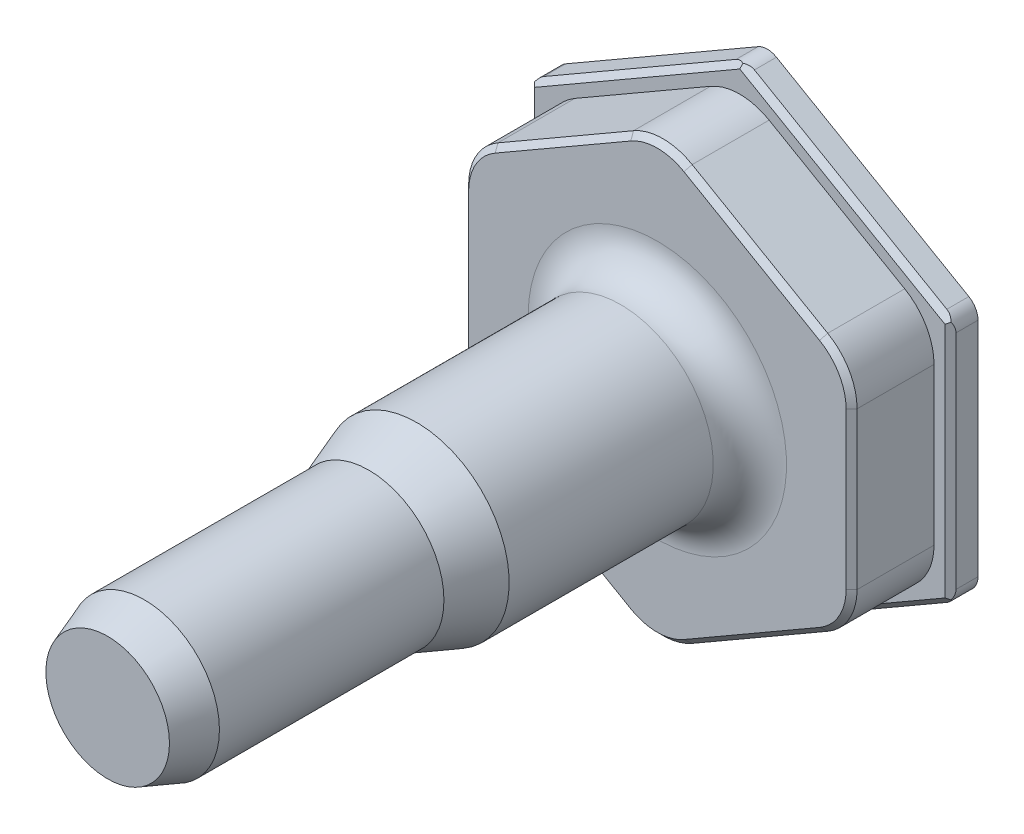
SolidWorks part; units mm, degrees
ref_plane "Front Plane" through (0, 0, 0) normal (0, 0, 1) x (1, 0, 0)
ref_plane "Top Plane" through (0, 0, 0) normal (0, 1, 0) x (1, 0, 0)
ref_plane "Right Plane" through (0, 0, 0) normal (1, 0, 0) x (0, 0, -1)
sketch "Sketch1" plane through (0, 0, 0) normal (0, 0, 1) x (1, 0, 0)
  line L12 (0, 12.2398) -> (10.6, 6.1199)
  line L14 (10.6, 6.1199) -> (10.6, -6.1199)
  line L15 (10.6, -6.1199) -> (0, -12.2398)
  line L16 (0, -12.2398) -> (-10.6, -6.1199)
  line L17 (-10.6, -6.1199) -> (-10.6, 6.1199)
  line L18 (-10.6, 6.1199) -> (0, 12.2398)
  line L19 (-11.5, 6.6395) -> (0, 13.2791)
  line L20 (0, 13.2791) -> (11.5, 6.6395)
  line L21 (11.5, 6.6395) -> (11.5, -6.6395)
  line L22 (11.5, -6.6395) -> (0, -13.2791)
  line L23 (0, -13.2791) -> (-11.5, -6.6395)
  line L24 (-11.5, -6.6395) -> (-11.5, 6.6395)
  circle A1 centre (0, 0) radius 3.25
  circle A2 centre (0, 0) radius 5.05
  circle A3 centre (0, 0) radius 2.125
  circle A4 centre (0, 0) radius 4.1
  point P3 (0, 12.2398)
  point P4 (10.6, 6.1199)
  point P7 (10.6, -6.1199)
  point P9 (0, -12.2398)
  point P10 (-10.6, -6.1199)
  point P12 (-10.6, 6.1199)
  point P13 (0, 0)
  dimension "D1" = 21.2
  dimension "D6" = 6.5
  dimension "D7" = 10.1
  dimension "D8" = 4.25
  dimension "D9" = 8.2
  dimension "D2" = 6
  dimension "D3" = 120
  dimension "D4" = 120
  dimension "D5" = 0.9
extrude "Boss-Extrude1" add sketch "Sketch1" along normal blind 1.5 contours L19 L20 L21 L22 L23 L24
ref_plane "Plane1" through (-11.5, -6.6395, 0) normal (-0.866, 0.5, 0) x (0, 0, 1)
ref_plane "Plane2" through (0, -13.2791, 0) normal (-0.866, 0.5, 0) x (0, 0, 1)
extrude "Boss-Extrude3" add sketch "Sketch1<8>" along normal blind 36 contours A4
sketch "Sketch1<8>" plane through (0, 0, 0) normal (0, 0, 1) x (1, 0, 0) same geometry as "Sketch1"
extrude "Boss-Extrude4" add sketch "Sketch1<9>" along normal blind 19 contours A2
sketch "Sketch1<9>" plane through (0, 0, 0) normal (0, 0, 1) x (1, 0, 0) same geometry as "Sketch1"
shell "Shell1" thickness 2
extrude "Cut-Extrude1" cut sketch "Sketch1<10>" along normal blind 17 contours A1
sketch "Sketch1<10>" plane through (0, 0, 0) normal (0, 0, 1) x (1, 0, 0) same geometry as "Sketch1"
extrude "Boss-Extrude2" add sketch "Sketch1<3>" along normal blind 6 contours L17 L18 L12 L14 L15 L16 | A1
sketch "Sketch1<3>" plane through (0, 0, 0) normal (0, 0, 1) x (1, 0, 0) same geometry as "Sketch1"
chamfer "Chamfer1" distance 2 angle 20 1 edges at (4.1, 0, 36) first distance on face at (4.1, 0, 19)
chamfer "Chamfer2" distance 1 angle 70 1 edges at (4.1, 0, 19) first distance on face at (4.1, 0, 19)
chamfer "Chamfer3" distance 0.7 angle 60 1 edges at (2.1, 0, 17) first distance on face at (2.1, 0, 17)
chamfer "Chamfer6" distance 0.3 angle 45 1 edges at (3.25, 0, 0)
ref_plane "Plane3" through (0, 0, 5) normal (0, 0, 1) x (1, 0, 0)
sketch "Sketch2" plane through (0, 0, 5) normal (0, 0, 1) x (1, 0, 0)
  line L1 (-17.7118, 13.112) -> (21.871, 13.112)
  line L2 (-17.7118, 13.112) -> (-17.7118, -17.4474)
  line L3 (-17.7118, -17.4474) -> (21.871, -17.4474)
  line L4 (21.871, 13.112) -> (21.871, -17.4474)
fillet "Fillet1" radius 3.2 6 edges at (10.6, -6.1199, 3.75) (0, -12.2398, 3.75) (-10.6, -6.1199, 3.75) (-10.6, 6.1199, 3.75) (0, 12.2398, 3.75) (10.6, 6.1199, 3.75)
chamfer "Chamfer5" distance 0.3 angle 45 18 edges at (-10.6, 0, 6) (-5.3, 9.1799, 6) (5.3, 9.1799, 6) (10.6, 0, 6) (5.3, -9.1799, 6) (-5.3, -9.1799, 6) (11.5, 0, 1.5) (5.75, -9.9593, 1.5) (-5.75, -9.9593, 1.5) (-11.5, 0, 1.5) (5.75, 9.9593, 1.5) (-5.75, 9.9593, 1.5) (0, -11.7448, 6) (-10.1713, -5.8724, 6) (-10.1713, 5.8724, 6) (0, 11.7448, 6) (10.1713, 5.8724, 6) (10.1713, -5.8724, 6)
fillet "Fillet2" radius 1 6 edges at (11.5, -6.6395, 0.6) (11.5, 6.6395, 0.6) (0, 13.2791, 0.6) (0, -13.2791, 0.6) (-11.5, -6.6395, 0.6) (-11.5, 6.6395, 0.6)
fillet "Fillet3" radius 2 1 edges at (-5.05, 0, 6)
